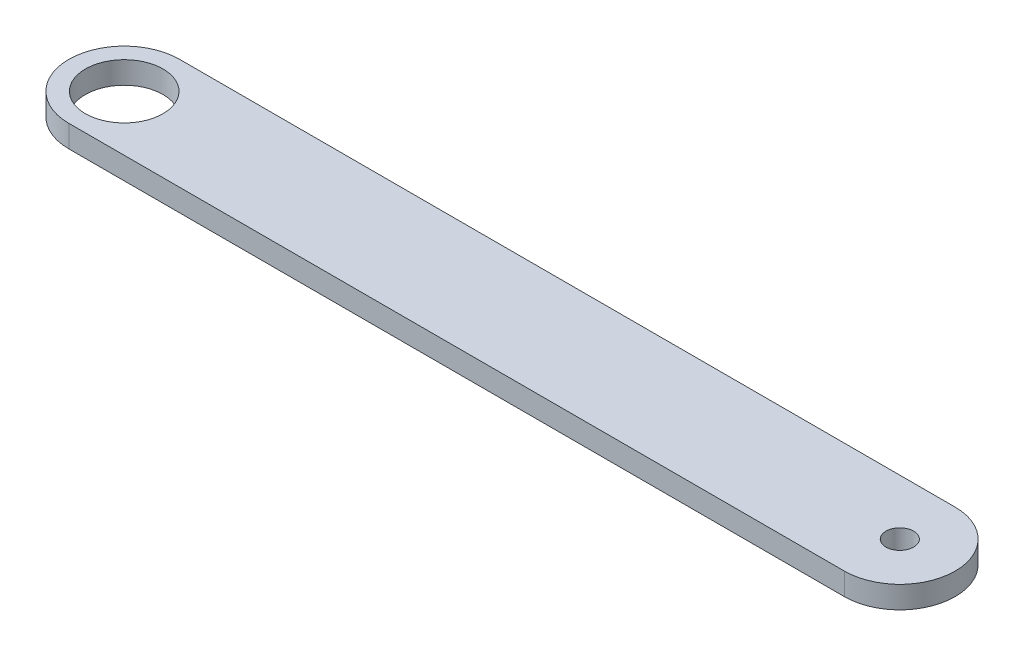
SolidWorks part; units mm, degrees
ref_plane "Front Plane" through (0, 0, 0) normal (0, 0, 1) x (1, 0, 0)
ref_plane "Top Plane" through (0, 0, 0) normal (0, 1, 0) x (1, 0, 0)
ref_plane "Right Plane" through (0, 0, 0) normal (1, 0, 0) x (0, 0, -1)
sketch "Sketch1" plane through (0, 0, 0) normal (0, 1, 0) x (1, 0, 0)
  line L0 (0, 10) -> (140, 10)
  line L1 (0, -10) -> (140, -10)
  circle A0 centre (0, 0) radius 7
  circle A1 centre (0, 0) radius 10
  circle A2 centre (140, 0) radius 2.5
  circle A4 centre (140, 0) radius 10
  dimension "D1" = 14
  dimension "D2" = 20
  dimension "D3" = 5
  dimension "D4" = 140
extrude "Boss-Extrude1" add sketch "Sketch1" along normal blind 4 contours A4 L0 A1 L1 | A1 A0 | A4 A2 region at (70, 0, 0) region at (6.8711, 0, -6.8711) region at (146.8711, 0, -6.8711)
equation "\"armLen\" = 140"
equation "\"D4@Sketch1\"=\"armLen\""
